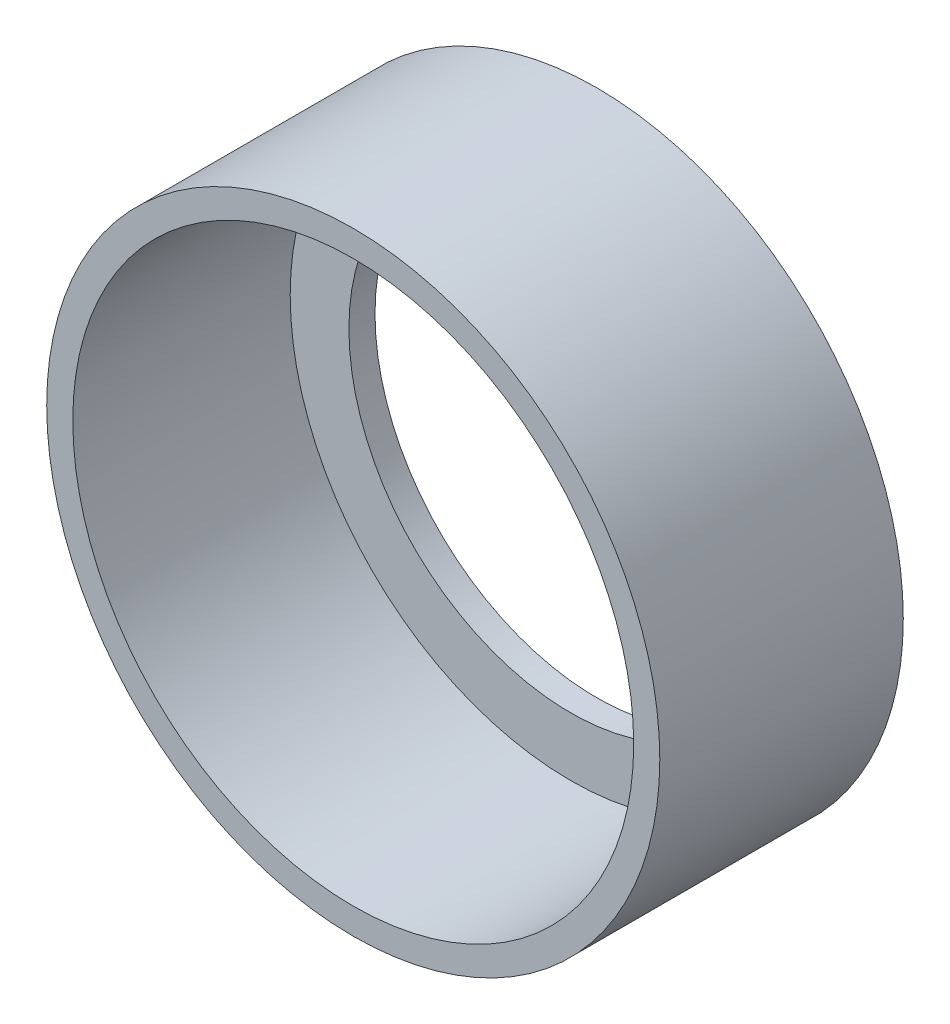
SolidWorks part; units mm, degrees
ref_plane "Front Plane" through (0, 0, 0) normal (0, 0, 1) x (1, 0, 0)
ref_plane "Top Plane" through (0, 0, 0) normal (0, 1, 0) x (1, 0, 0)
ref_plane "Right Plane" through (0, 0, 0) normal (1, 0, 0) x (0, 0, -1)
sketch "Sketch1" plane through (0, 0, 0) normal (0, 1, 0) x (1, 0, 0)
  line L0 (0, 10.179) -> (0, 0) construction
  line L1 (16.383, 5.4256) -> (17.907, 5.4256)
  line L2 (17.907, 5.4256) -> (17.907, 19.6496)
  line L3 (17.907, 19.6496) -> (12.954, 19.6496)
  line L4 (12.954, 19.6496) -> (12.954, 18.1256)
  line L5 (12.954, 18.1256) -> (16.383, 18.1256)
  line L6 (16.383, 18.1256) -> (16.383, 5.4256)
  dimension "D1" = 1.524
  dimension "D2" = 16.383
  dimension "D3" = 12.954
  dimension "D4" = 1.524
  dimension "D5" = 12.7
revolve "Revolve1" add sketch "Sketch1" angle 360 about L0
